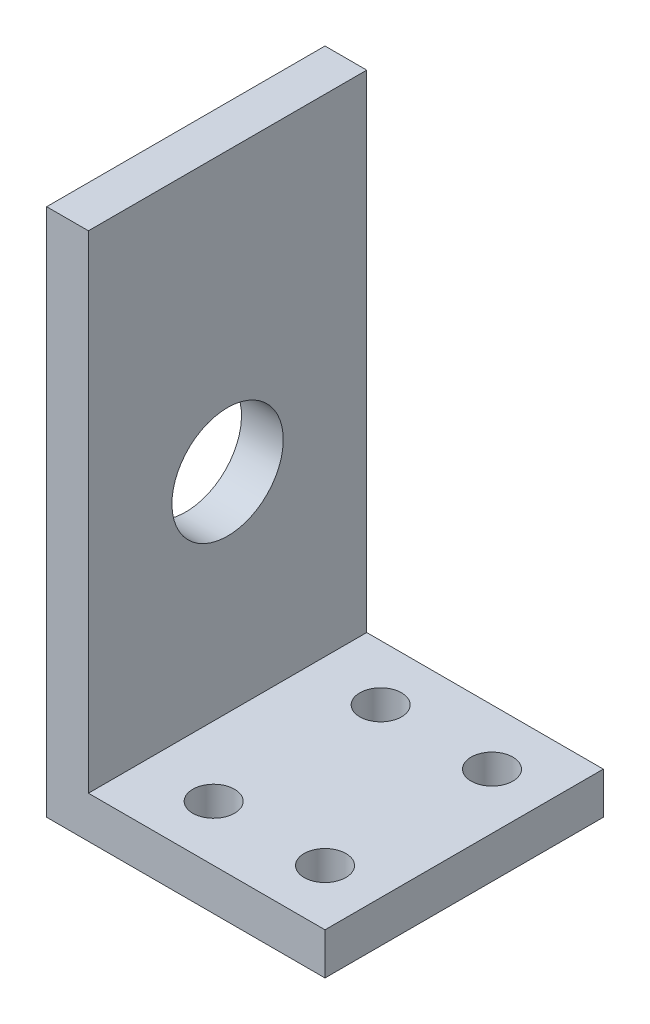
SolidWorks part; units mm, degrees
ref_plane "Front" through (0, 0, 0) normal (0, 0, 1) x (1, 0, 0)
ref_plane "Top" through (0, 0, 0) normal (0, 1, 0) x (1, 0, 0)
ref_plane "Right" through (0, 0, 0) normal (1, 0, 0) x (0, 0, -1)
sketch "草图1" plane through (0, 0, 0) normal (0, 0, 1) x (1, 0, 0)
  line L0 (0, 0) -> (0, 38)
  line L1 (0, 38) -> (3, 38)
  line L2 (3, 38) -> (3, 3)
  line L3 (3, 3) -> (20, 3)
  line L4 (20, 3) -> (20, 0)
  line L5 (20, 0) -> (0, 0)
  dimension "D1" = 38
  dimension "D2" = 3
  dimension "D3" = 35
  dimension "D4" = 17
extrude "凸台-拉伸1" add sketch "草图1" along normal blind 20
sketch "草图2" plane through (0, 3, 0) normal (0, 1, 0) x (1, 0, 0)
  line L0 (16, 0) -> (16, -20) construction
  line L1 (20, 0) -> (3, 0) construction
  line L2 (20, -20) -> (3, -20) construction
  line L3 (20, -20) -> (20, 0) construction
  circle A0 centre (16, -16) radius 1.5
  circle A1 centre (16, -4) radius 1.5
  dimension "D2" = 3
  dimension "D3" = 3
  dimension "D1" = 4
  dimension "D4" = 12
  dimension "D5" = 4
extrude "切除-拉伸1" cut sketch "草图2" against normal through all
sketch "草图3" plane through (3, 0, 0) normal (1, 0, 0) x (0, 0, -1)
  circle A0 centre (-10, 18) radius 4
  dimension "D1" = 8
extrude "切除-拉伸2" cut sketch "草图3" against normal through all
sketch "草图4" plane through (0, 3, 0) normal (0, 1, 0) x (1, 0, 0)
  circle A0 centre (8, -16) radius 1.5
  circle A1 centre (8, -4) radius 1.5
  dimension "D3" = 3
extrude "切除-拉伸3" cut sketch "草图4" against normal blind 20
